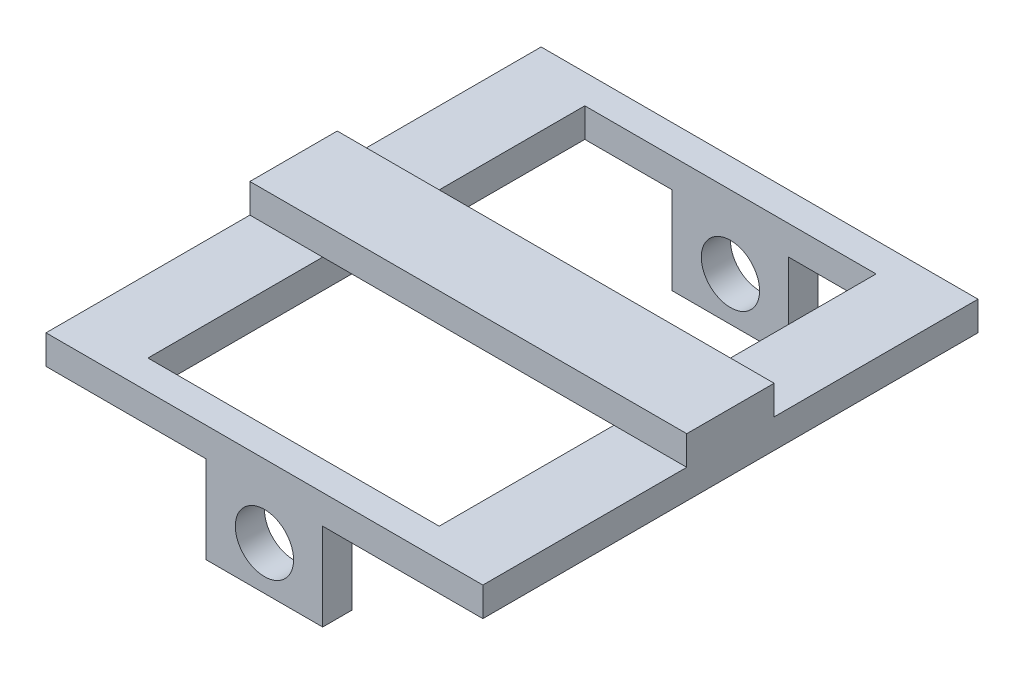
SolidWorks part; units mm, degrees
ref_plane "Front Plane" through (0, 0, 0) normal (0, 0, 1) x (1, 0, 0)
ref_plane "Top Plane" through (0, 0, 0) normal (0, 1, 0) x (1, 0, 0)
ref_plane "Right Plane" through (0, 0, 0) normal (1, 0, 0) x (0, 0, -1)
sketch "Sketch1" plane through (0, 0, 0) normal (0, 1, 0) x (1, 0, 0)
  line L1 (0, 0) -> (-150, 0)
  line L2 (0, 0) -> (0, 30)
  line L3 (0, 30) -> (-150, 30)
  line L4 (-150, 0) -> (-150, 30)
  dimension "D1" = 30
  dimension "D2" = 150
extrude "Boss-Extrude1" add sketch "Sketch1" along normal blind 10
sketch "Sketch8" plane through (0, 0, 0) normal (0, -1, 0) x (-1, 0, 0)
  line L0 (150, 0) -> (0, 30)
  line L1 (150, 30) -> (0, 0)
  line L2 (150, 0) -> (0, 0) construction
sketch "Sketch9" plane through (0, 0, 0) normal (0, -1, 0) x (1, 0, 0)
  line L0 (-150, -30) -> (0, 0) construction
  line L1 (0, -100) -> (-150, -100)
  line L2 (0, -100) -> (0, 70)
  line L3 (0, 70) -> (-150, 70)
  line L4 (-150, -100) -> (-150, 70)
  line L5 (0, -100) -> (-150, 70) construction
  line L6 (0, 70) -> (-150, -100) construction
  line L8 (-125, -90) -> (-25, -90)
  line L9 (-125, -90) -> (-125, 60)
  line L10 (-125, 60) -> (-25, 60)
  line L11 (-25, -90) -> (-25, 60)
  line L12 (-125, -90) -> (-25, 60) construction
  line L13 (-125, 60) -> (-25, -90) construction
  point P0 (-75, -15)
  point P7 (-75, -15)
  dimension "D1" = 170
  dimension "D2" = 150
  dimension "D3" = 150
  dimension "D4" = 100
extrude "Boss-Extrude3" add sketch "Sketch9" along normal blind 10
sketch "Sketch10" plane through (0, -10, 0) normal (0, -1, 0) x (1, 0, 0)
  line L0 (-75, 70) -> (-75, -100)
  line L1 (0, 70) -> (-150, 70) construction
  line L2 (-150, -100) -> (0, -100) construction
  line L3 (-150, -15) -> (0, -15)
  line L4 (-150, 70) -> (-150, -100) construction
  line L5 (0, -100) -> (0, 70) construction
  line L6 (-125, 60) -> (-25, 60)
  line L7 (-25, 60) -> (-75, 60)
  line L8 (-75, 60) -> (-75, 70)
sketch "Sketch12" plane through (0, -10, 0) normal (0, -1, 0) x (1, 0, 0)
  line L0 (-55, -100) -> (-55, -90)
  line L1 (-75, 70) -> (-55, 70)
  line L2 (-125, -90) -> (-25, -90) construction
  line L3 (-75, 60) -> (-55, 60)
  line L4 (-55, 70) -> (-55, 60)
  line L5 (-75, 60) -> (-95, 60)
  line L6 (-75, -100) -> (-55, -100)
  line L7 (-75, 70) -> (-95, 70)
  line L8 (-95, 60) -> (-95, 70)
  line L9 (0, 70) -> (-150, 70) construction
  line L10 (-75, -100) -> (-95, -100)
  line L11 (-95, -100) -> (-95, -90)
  line L12 (-75, -90) -> (-95, -90)
  line L16 (-75, -90) -> (-55, -90)
  dimension "D1" = 10
  dimension "D2" = 20
  dimension "D3" = 10
  dimension "D4" = 20
extrude "Boss-Extrude5" add sketch "Sketch12" along normal blind 30
sketch "Sketch15" plane through (0, 0, 70) normal (0, 0, 1) x (1, 0, 0)
  line L0 (-95, -40) -> (-55, -10)
  line L1 (-55, -40) -> (-95, -10)
sketch "Sketch16" plane through (0, 0, 70) normal (0, 0, 1) x (1, 0, 0)
  circle A0 centre (-75, -25) radius 10
  dimension "D1" = 20
extrude "Cut-Extrude2" cut sketch "Sketch16" against normal blind 170
sketch "Sketch14" plane through (0, 0, -100) normal (0, 0, -1) x (-1, 0, 0)
  circle A0 centre (75, -30) radius 10
  dimension "D1" = 20
